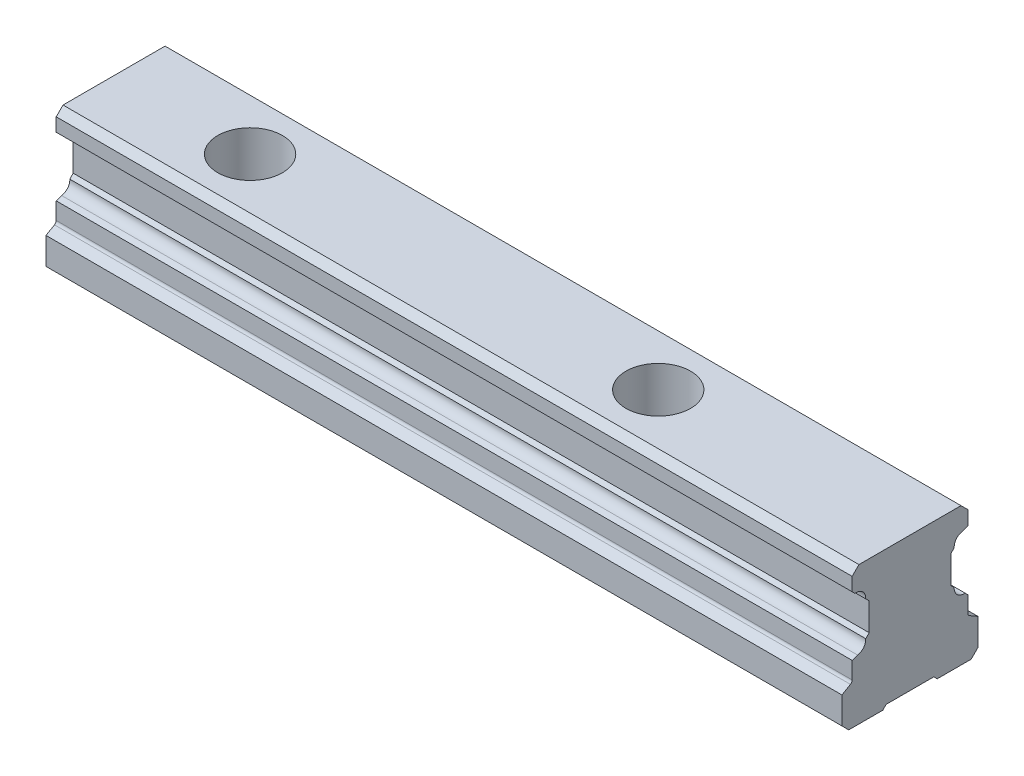
SolidWorks part; units mm, degrees
ref_plane "Front Plane" through (0, 0, 0) normal (0, 0, 1) x (1, 0, 0)
ref_plane "Top Plane" through (0, 0, 0) normal (0, 1, 0) x (1, 0, 0)
ref_plane "Right Plane" through (0, 0, 0) normal (1, 0, 0) x (0, 0, -1)
ref_plane "Plane1" through (58.5, 0, 0) normal (1, 0, 0) x (0, 0, -1)
sketch "Sketch1" plane through (58.5, 0, 0) normal (1, 0, 0) x (0, 0, -1)
  line L0 (-8.5, 0) -> (8.5, 0)
  line L1 (8.5, 0) -> (8.5, 9.0051)
  line L2 (6.5033, 10.3667) -> (6, 10.87)
  line L3 (6, 10.87) -> (6, 14.93)
  line L4 (6, 14.93) -> (6.5033, 15.4333)
  line L5 (8.5, 16.7949) -> (8.5, 20.3)
  line L6 (8.5, 20.3) -> (-8.5, 20.3)
  line L7 (-8.5, 20.3) -> (-8.5, 16.7949)
  line L8 (-6.5033, 15.4333) -> (-6, 14.93)
  line L9 (-6, 14.93) -> (-6, 10.87)
  line L10 (-6, 10.87) -> (-6.5033, 10.3667)
  line L11 (-8.5, 9.0051) -> (-8.5, 0)
  arc A0 (8.5, 9.0051) -> (6.5033, 10.3667) centre (7.9, 10.27) cw
  arc A1 (6.5033, 15.4333) -> (8.5, 16.7949) centre (7.9, 15.53) cw
  arc A2 (-8.5, 16.7949) -> (-6.5033, 15.4333) centre (-7.9, 15.53) cw
  arc A3 (-6.5033, 10.3667) -> (-8.5, 9.0051) centre (-7.9, 10.27) cw
extrude "Boss-Extrude1" add sketch "Sketch1" against normal blind 117
sketch "Sketch2" plane through (0, 0, -8.5) normal (0, 0, -1) x (-1, 0, 0)
  line L0 (58.5, 5.816) -> (58.5, 0)
  line L1 (58.5, 0) -> (-58.5, 0)
  line L2 (-58.5, 0) -> (-58.5, 5.816)
  line L3 (-58.5, 5.816) -> (58.5, 5.816)
  line L4 (-58.5, 0) -> (-58.5, 9.0051) construction
  line L5 (58.5, 0) -> (58.5, 9.0051) construction
extrude "Boss-Extrude2" add sketch "Sketch2" along normal blind 1.5
sketch "Sketch3" plane through (0, 0, 8.5) normal (0, 0, 1) x (1, 0, 0)
  line L0 (-58.5, 0) -> (-58.5, 4.95)
  line L1 (-58.5, 4.95) -> (58.5, 4.95)
  line L2 (58.5, 4.95) -> (58.5, 0)
  line L3 (58.5, 0) -> (-58.5, 0)
  line L4 (-58.5, 9.0051) -> (-58.5, 0) construction
  line L5 (58.5, 9.0051) -> (58.5, 0) construction
extrude "Boss-Extrude3" add sketch "Sketch3" along normal blind 1.5
sketch "Sketch4" plane through (-58.5, 0, 0) normal (-1, 0, 0) x (0, 0, 1)
  line L0 (-3.5, 0) -> (3.5, 0)
  line L1 (3.5, 0) -> (3.5, 0.5)
  line L2 (3.5, 0.5) -> (-3.5, 0.5)
  line L3 (-3.5, 0.5) -> (-3.5, 0)
extrude "Cut-Extrude1" cut sketch "Sketch4" against normal through all
draft "Draft1" type of draft neutral plane draft angle 30 faces to draft 1 face at (0, 4.95, 9.25) neutral plane through (0, 0, 10) neutral plane normal (0, 0, 1) parameters "D1"=30
draft "Draft2" type of draft neutral plane draft angle 30 faces to draft 1 face at (0, 5.816, -9.25) neutral plane through (-58.5, 0, -8.5) neutral plane normal (0, 0, -1) parameters "D1"=30
draft "Draft3" type of draft neutral plane draft angle 45 faces to draft 2 face at (0, 0.25, 3.5) face at (0, 0.25, -3.5) neutral plane through (58.5, 0.5, 3.5) neutral plane normal (0, -1, 0) parameters "D1"=45
hole_wizard "Hole1" positions "Sketch6" profile "Sketch5" legacy
sketch "Sketch6" plane through (0, 20.3, 0) normal (0, 1, 0) x (-1, 0, 0)
  point P0 (38.5, 0)
  point P1 (-21.5, 0)
sketch "Sketch5" plane through (-38.5, 20.3, 0) normal (1, 0, 0) x (0, 0, 1)
  line L0 (0, 0) -> (0, 20.3)
  line L1 (0, 20.3) -> (3, 20.3)
  line L2 (3, 20.3) -> (3, 8.5)
  line L3 (3, 8.5) -> (4.75, 8.5)
  line L4 (4.75, 8.5) -> (4.75, 0)
  line L5 (4.75, 0) -> (0, 0)
  line L6 (0, 110) -> (0, -10) construction
  dimension "Diameter" = 6
  dimension "Depth" = 20.3
  dimension "C-Bore Diameter" = 9.5
  dimension "C-Bore Depth" = 8.5
chamfer "Chamfer1" distance 1 angle 45 4 edges at (0, 20.3, 8.5) (0, 0, -10) (0, 0, 10) (0, 20.3, -8.5)
chamfer "Chamfer2" distance 0.5382 angle 45 4 edges at (0, 9.0051, 8.5) (0, 16.7949, 8.5) (0, 16.7949, -8.5) (0, 9.0051, -8.5) first distance on face at (0, 9.3996, 7.3065) first distance on face at (0, 18.0475, 8.5) first distance on face at (0, 16.4004, -7.3065) first distance on face at (0, 7.4106, -8.5)
fillet "Fillet1" radius 0.5 2 edges at (0, 5.816, 8.5) (0, 5.816, -8.5) tangent propagation no
